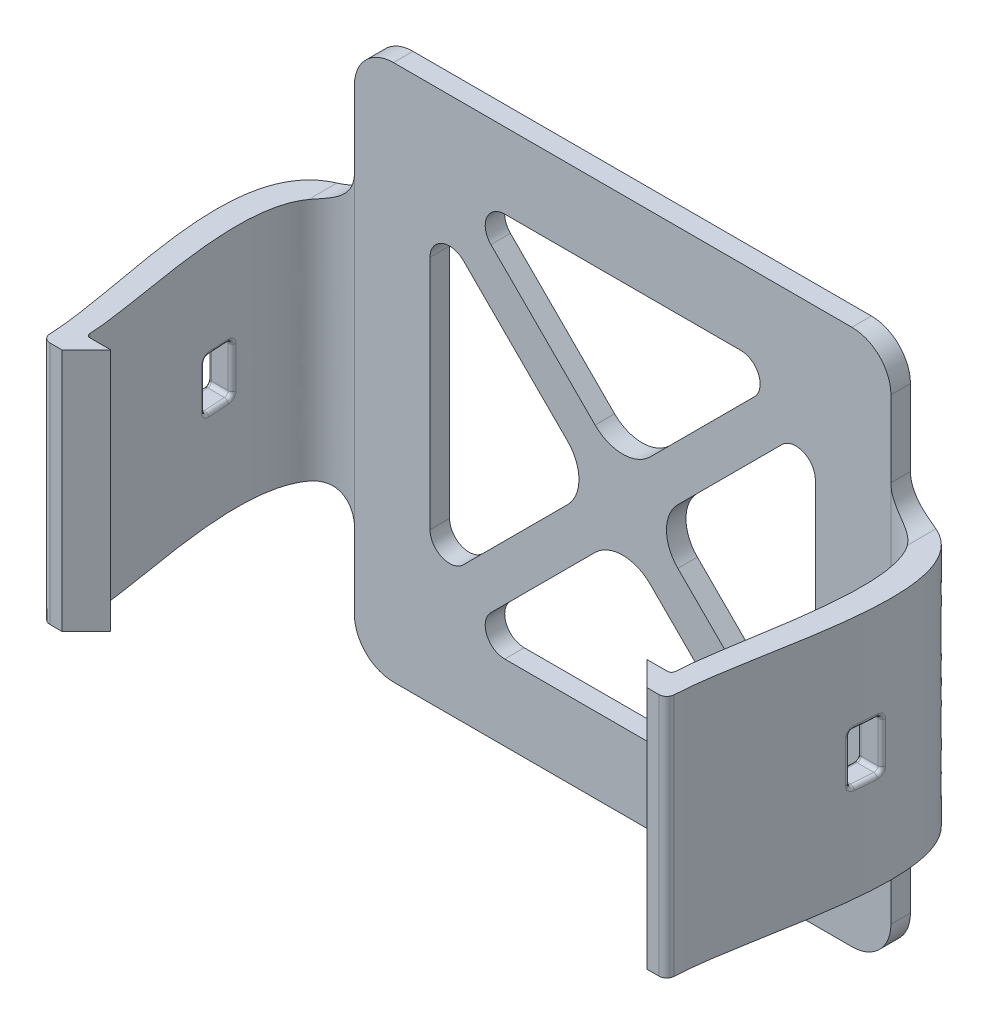
SolidWorks part; units mm, degrees
ref_plane "Front Plane" through (0, 0, 0) normal (0, 0, 1) x (1, 0, 0)
ref_plane "Top Plane" through (0, 0, 0) normal (0, 1, 0) x (1, 0, 0)
ref_plane "Right Plane" through (0, 0, 0) normal (1, 0, 0) x (0, 0, -1)
sketch "Sketch1" plane through (0, 0, 0) normal (0, 0, 1) x (1, 0, 0)
  line L0 (-35.6221, 10.9987) -> (8.3779, -33.0013) construction
  line L1 (-35.6221, -33.0013) -> (8.3779, 10.9987) construction
  line L2 (-33.3721, 5.9203) -> (-16.4505, -11.0013)
  line L3 (-41.1221, 16.4987) -> (13.8779, 16.4987)
  line L4 (-41.1221, 16.4987) -> (-41.1221, -38.5013)
  line L5 (-41.1221, -38.5013) -> (13.8779, -38.5013)
  line L6 (13.8779, 16.4987) -> (13.8779, -38.5013)
  line L7 (-41.1221, 16.4987) -> (13.8779, -38.5013) construction
  line L8 (-41.1221, -38.5013) -> (13.8779, 16.4987) construction
  line L9 (-30.5436, 8.7487) -> (3.2995, 8.7487)
  line L10 (-33.3721, 5.9203) -> (-33.3721, -27.9229)
  line L11 (-30.5436, -30.7513) -> (3.2995, -30.7513)
  line L12 (6.1279, 5.9203) -> (6.1279, -27.9229)
  line L13 (-32.1221, 7.4987) -> (4.8779, -29.5013) construction
  line L14 (-32.1221, -29.5013) -> (4.8779, 7.4987) construction
  line L15 (-30.5436, 8.7487) -> (-13.6221, -8.1729)
  line L16 (-33.3721, -27.9229) -> (-16.4505, -11.0013)
  line L17 (6.1279, 5.9203) -> (-10.7936, -11.0013)
  line L18 (-13.6221, -8.1729) -> (3.2995, 8.7487)
  line L19 (-13.6221, -13.8297) -> (-30.5436, -30.7513)
  line L20 (-13.6221, -13.8297) -> (3.2995, -30.7513)
  line L21 (-10.7936, -11.0013) -> (6.1279, -27.9229)
  point P12 (-13.6221, -11.0013)
  point P17 (-13.6221, -11.0013)
  dimension "D3" = 7.75
  dimension "D4" = 7.75
  dimension "D5" = 7.75
  dimension "D6" = 7.75
  dimension "D1" = 44
  dimension "D2" = 44
  dimension "D11" = 55
  dimension "D12" = 55
  dimension "D13" = 37
  dimension "D14" = 2
  dimension "D15" = 2
  dimension "D16" = 2
  dimension "D17" = 2
extrude "Boss-Extrude1" add sketch "Sketch1" along normal blind 2
fillet "Fillet1" radius 4 4 edges at (-41.1221, 16.4987, 1) (13.8779, -38.5013, 1) (13.8779, 16.4987, 1) (-41.1221, -38.5013, 1)
fillet "Fillet3" radius 2 8 edges at (-30.5436, 8.7487, 1) (3.2995, 8.7487, 1) (6.1279, 5.9203, 1) (6.1279, -27.9229, 1) (3.2995, -30.7513, 1) (-30.5436, -30.7513, 1) (-33.3721, -27.9229, 1) (-33.3721, 5.9203, 1)
fillet "Fillet4" radius 4 4 edges at (-13.6221, -8.1729, 1) (-16.4505, -11.0013, 1) (-13.6221, -13.8297, 1) (-10.7936, -11.0013, 1)
ref_plane "Plane1" through (0, -11.0013, 0) normal (0, 1, 0) x (1, 0, 0)
sketch "Sketch2" plane through (0, -11.0013, 0) normal (0, 1, 0) x (1, 0, 0)
  line L0 (-41.1221, 0) -> (-41.1221, -2) construction
  line L1 (-41.1221, 0) -> (-41.1221, -2)
  line L2 (-43.6221, -27) -> (-41.1221, -27)
  line L3 (-41.1221, -27) -> (-43.6221, -29.5)
  line L4 (-36.4648, -2) -> (-45.7794, -2) construction
  line L5 (-43.6221, -6.2293) -> (-43.6221, -15.981) construction
  line L6 (-43.6221, -29.5) -> (-45.6221, -29.5)
  line L8 (-45.6221, -6.3491) -> (-45.6221, -20.8613) construction
  line L9 (-37.1221, -2) -> (9.8779, -2) construction
  line L10 (-31.0321, 0) -> (-51.212, 0) construction
  spline S0 degree 3 poles (-43.6221, -27) (-43.6221, -20.9052) (-49.5974, -2) (-41.1221, -2) knots 0 0 0 0 1 1 1 1
  spline S1 degree 3 poles (-45.6221, -29.5) (-45.6221, -20.4298) (-53.7345, 0) (-41.1221, 0) knots 0 0 0 0 1 1 1 1
  point P14 (0, 0)
  dimension "D1" = 2.5
  dimension "D2" = 2.5
  dimension "D3" = 2.5
  dimension "D4" = 2
  dimension "D5" = 25
extrude "Boss-Extrude2" add sketch "Sketch2" along normal blind 12.5 and the other way blind 12.5
ref_plane "Plane2" through (-13.6221, 0, 0) normal (1, 0, 0) x (0, 0, -1)
mirror "Mirror2" about plane through (-13.6221, 0, 0) normal (1, 0, 0) of "Boss-Extrude2"
fillet "Fillet5" radius 3.2 4 edges at (-41.1221, 1.4987, 1) (-41.1221, -23.5013, 1) (13.8779, 1.4987, 1) (13.8779, -23.5013, 1)
fillet "Fillet6" radius 0.4 2 edges at (16.3779, -11.0013, 27) (-43.6221, -11.0013, 27)
fillet "Fillet7" radius 0.8 2 edges at (-45.6221, -11.0013, 29.5) (18.3779, -11.0013, 29.5)
sketch "Sketch3" plane through (0, 0, 0) normal (1, 0, 0) x (0, 0, -1)
  line L0 (-2, -26.7013) -> (-2, 4.6987) construction
  line L1 (-13, -8.5013) -> (-10, -8.5013)
  line L2 (-13, -8.5013) -> (-13, -13.5013)
  line L3 (-13, -13.5013) -> (-10, -13.5013)
  line L4 (-10, -8.5013) -> (-10, -13.5013)
  line L5 (-13, -8.5013) -> (-10, -13.5013) construction
  line L6 (-13, -13.5013) -> (-10, -8.5013) construction
  point P0 (-11.5, -11.0013)
  point P7 (-2, -11.0013)
  dimension "D1" = 8
  dimension "D2" = 3
  dimension "D3" = 5
extrude "Cut-Extrude1" cut sketch "Sketch3" against normal through all and the other way through all
fillet "Fillet8" radius 0.4 24 edges at (20.93, -11.0013, 10) (20.7064, -11.0013, 13) (18.2375, -11.0013, 13) (18.4187, -11.0013, 10) (-48.1741, -11.0013, 10) (-45.6629, -11.0013, 10) (-45.4816, -11.0013, 13) (-47.9505, -11.0013, 13) (19.6743, -8.5013, 10) (19.472, -8.5013, 13) (19.472, -13.5013, 13) (19.6743, -13.5013, 10) (-46.7161, -8.5013, 13) (-46.9185, -8.5013, 10) (-46.9185, -13.5013, 10) (-46.7161, -13.5013, 13)
